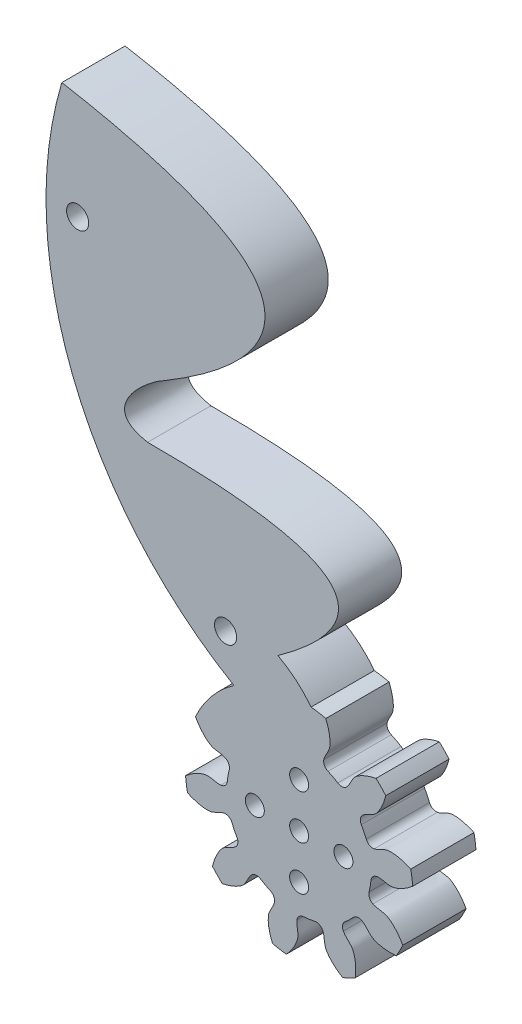
SolidWorks part; units mm, degrees
material "3003 Alaşım"
ref_plane "前视基准面" through (0, 0, 0) normal (0, 0, 1) x (1, 0, 0)
ref_plane "上视基准面" through (0, 0, 0) normal (0, 1, 0) x (1, 0, 0)
ref_plane "右视基准面" through (0, 0, 0) normal (1, 0, 0) x (0, 0, -1)
sketch "草图1" plane through (0, 0, 0) normal (0, 0, 1) x (1, 0, 0)
  line L0 (-50.4998, 0) -> (-25.4998, 0) construction
  line L1 (-25, 74.7114) -> (-25, -57.8833) construction
  line L31 (-25, -57.0526) -> (-25, -57.8833)
  line L34 (-25, -66.5436) -> (-15, -66.5436) construction
  arc A0 (-57.4998, 17.1398) -> (-27.1875, -53.4868) centre (0, 0) ccw
  arc A17 (-23.3522, -44.2117) -> (-14.8293, -57.9841) centre (-30.8249, -58.3594) cw
  arc A18 (-25, -57.8833) -> (-14.8293, -57.9841) centre (-20, -66.5436) ccw
  arc A20 (-27.1875, -53.4868) -> (-25, -57.0526) centre (-29, -57.0526) cw
  circle A22 centre (-20, -66.5436) radius 5
  circle A26 centre (-31.6201, -45.0019) radius 1.75
  circle A27 centre (-55, 0) radius 1.75
  spline S0 degree 2 poles (-43.9459, -25.3211) (3.2013, -25.2078) (-23.3522, -44.2117) knots 0 0 0 1 1 1
  spline S1 degree 3 poles (-41.4745, -15.6627) (-44.1246, -17.0533) (-52.2417, -23.8081) (-43.9459, -25.3211) knots 0 0 0 0 1 1 1 1
  spline S2 degree 2 poles (-57.4998, 17.1398) (-2.6788, 7.4257) (-41.4745, -15.6627) knots 0 0 0 1 1 1
  point P9 (-25.4998, 0)
  point P64 (-25, -54.5436)
  point P69 (0, 0)
  dimension "D1" = 60
  dimension "D4" = 32
  dimension "D6" = 16
  dimension "D7" = 4
  dimension "D9" = 10
  dimension "D10" = 3.5
  dimension "D3" = 25
extrude "凸台拉伸1" add sketch "草图1" along normal blind 1
extrude "凸台-拉伸1" add sketch "草图1<2>" along normal blind 10
sketch "草图1<2>" plane through (0, 0, 0) normal (0, 0, 1) x (1, 0, 0) same geometry as "草图1"
ref_plane "基准面1" through (-57.4998, 17.1398, 10) normal (-0.9847, 0.1745, 0) x (0, 0, 1)
sketch "草图2" plane through (0, 0, 10) normal (0, 0, 1) x (1, 0, 0)
  line L0 (-20, -66.5436) -> (-20, -48.5436) construction
  arc A0 (-31.0412, -63.7058) -> (-31.3459, -65.4339) centre (-20, -66.5436) ccw
  arc A1 (-37.274, -57.0773) -> (-39.4699, -69.5309) centre (-20, -66.5436) ccw
  arc A2 (-31.3459, -65.4339) -> (-32.3704, -66.4576) centre (-32.4805, -65.3229) cw
  arc A3 (-31.6538, -62.3934) -> (-31.0412, -63.7058) centre (-32.1453, -63.422) cw
  circle A4 centre (-20, -66.5436) radius 14.5222 construction
  circle A5 centre (-20, -66.5436) radius 18 construction
  circle A6 centre (-20, -66.5436) radius 11.4 construction
  circle A7 centre (-20, -66.5436) radius 15 construction
  spline S0 degree 3 poles (-31.6538, -62.3934) (-32.2993, -62.085) (-33.153, -62.1602) (-33.8892, -61.824) (-33.9929, -61.7667) (-34.0741, -61.7189) (-34.166, -61.6606) (-34.268, -61.5914) (-34.3795, -61.5105) (-34.4998, -61.4172) (-34.6284, -61.3109) (-34.7644, -61.1911) (-34.9071, -61.0571) (-35.0558, -60.9084) (-35.2097, -60.7445) (-35.3679, -60.5649) (-35.5296, -60.3693) (-35.6939, -60.1571) (-35.8599, -59.9282) (-36.0268, -59.6821) (-36.1935, -59.4187) (-36.3593, -59.1376) (-36.523, -58.8386) (-36.6838, -58.5218) (-36.8406, -58.1869) (-37.047, -57.7073) (-37.1869, -57.3336) (-37.274, -57.0773) knots 0.111786 0.111786 0.111786 0.111786 0.344236 0.363717 0.372294 0.382431 0.394128 0.407384 0.422199 0.438574 0.456508 0.476002 0.497056 0.519669 0.543841 0.569573 0.596865 0.625716 0.656126 0.688097 0.721626 0.756715 0.793364 0.831572 0.87134 0.912667 1 1 1 1
  spline S1 degree 3 poles (-32.3704, -66.4576) (-33.0825, -66.5266) (-33.859, -66.164) (-34.6658, -66.2281) (-34.7828, -66.2465) (-34.8755, -66.2637) (-34.9817, -66.287) (-35.1012, -66.3171) (-35.2337, -66.355) (-35.3787, -66.4015) (-35.5359, -66.4574) (-35.7047, -66.5235) (-35.8846, -66.6006) (-36.0752, -66.6895) (-36.2758, -66.7909) (-36.4859, -66.9055) (-36.7048, -67.0341) (-36.9317, -67.1772) (-37.166, -67.3356) (-37.407, -67.5097) (-37.6538, -67.7003) (-37.9057, -67.9077) (-38.1618, -68.1326) (-38.4213, -68.3754) (-38.6832, -68.6365) (-39.0412, -69.0165) (-39.3004, -69.3198) (-39.4699, -69.5309) knots 0.111786 0.111786 0.111786 0.111786 0.344236 0.363717 0.372294 0.382431 0.394128 0.407384 0.422199 0.438574 0.456508 0.476002 0.497056 0.519669 0.543841 0.569573 0.596865 0.625716 0.656126 0.688097 0.721626 0.756715 0.793364 0.831572 0.87134 0.912667 1 1 1 1
  dimension "D1" = 1.14
  dimension "D2" = 29.0444
  dimension "D3" = 36
  dimension "D4" = 22.8
  dimension "D5" = 30
sketch "草图3" plane through (0, 0, 10) normal (0, 0, 1) x (1, 0, 0)
  circle A0 centre (-20, -66.5436) radius 18
extrude "凸台-拉伸2" add sketch "草图3" against normal blind 10
extrude "切除-拉伸1" cut sketch "草图2" against normal blind 10
sketch "草图4" plane through (0, 0, 10) normal (0, 0, 1) x (1, 0, 0)
  circle A0 centre (-20, -66.5436) radius 1.5
  circle A1 centre (-20, -59.5436) radius 1.5
  circle A2 centre (-13, -66.5436) radius 1.5
  circle A3 centre (-20, -73.5436) radius 1.5
  circle A4 centre (-27, -66.5436) radius 1.5
  point P14 (-20, -66.5436)
  dimension "D1" = 7
  dimension "D2" = 4
extrude "切除-拉伸2" cut sketch "草图4" against normal blind 10
pattern_circular "阵列(圆周)1" count 8 every 36 about axis through (-20, -66.5436, 0) along (0, 0, 1) of "切除-拉伸1"
